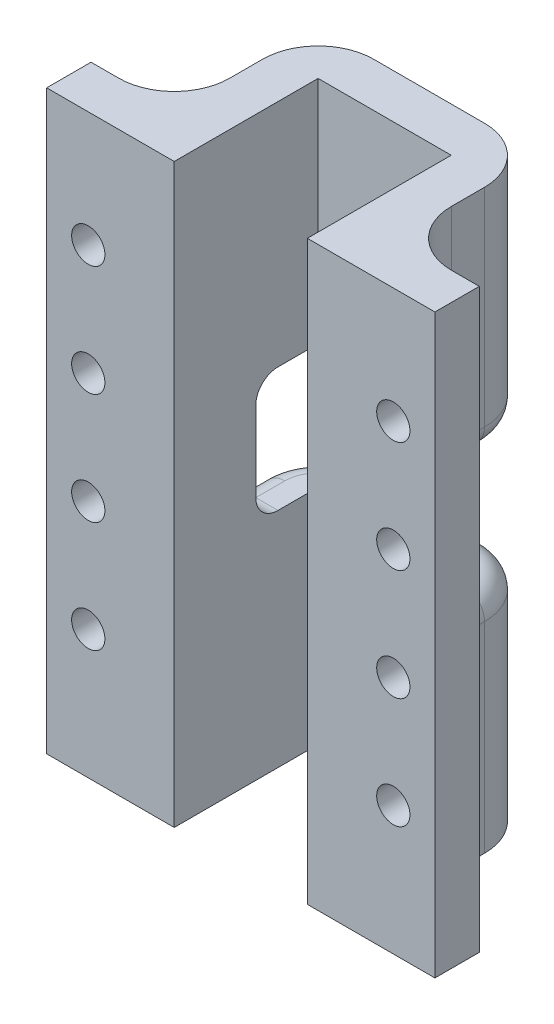
SolidWorks part; units mm, degrees
ref_plane "Спереди" through (0, 0, 0) normal (0, 0, 1) x (1, 0, 0)
ref_plane "Сверху" through (0, 0, 0) normal (0, 1, 0) x (1, 0, 0)
ref_plane "Справа" through (0, 0, 0) normal (1, 0, 0) x (0, 0, -1)
sketch "Эскиз1" plane through (0, 0, 0) normal (0, 1, 0) x (1, 0, 0)
  line L0 (-17.5, -8.4853) -> (-6, -8.4853)
  line L2 (-6, -8.4853) -> (-6, 4.5147)
  line L3 (-6, 4.4853) -> (6, 4.4853)
  line L4 (6, -8.4853) -> (6, 4.4853)
  line L5 (6, -8.4853) -> (17.5, -8.4853)
  line L6 (17.5, -8.4853) -> (17.5, -4.4853)
  line L7 (17.5, -4.4853) -> (10, -4.4853)
  line L8 (10, -4.4853) -> (10, 8.4853)
  line L9 (10, 8.4853) -> (-10, 8.4853)
  line L10 (-10, 8.4853) -> (-10, -4.4853)
  line L11 (-10, -4.4853) -> (-17.5, -4.4853)
  line L12 (-17.5, -4.4853) -> (-17.5, -8.4853)
  dimension "D1" = 11.5
  dimension "D2" = 4
  dimension "D3" = 12.9706
  dimension "D4" = 4
  dimension "D5" = 4
  dimension "D6" = 12.9706
extrude "Бобышка-Вытянуть1" add sketch "Эскиз1" along normal blind 52 contours L11 L12 L0 L2 L3 L4 L5 L6 L7 L8 L9 L10 | L3 L4 L5 L6 L7 L8 L9 L10 L11 L12 L0 L2 region at (-17.111, 0, 6.4853)
fillet "Скругление1" radius 5 4 edges at (-10, 26, -8.4853) (10, 26, -8.4853) (-10, 26, 4.4853) (10, 26, 4.4853)
ref_plane "Плоскость1" through (0, 0, 18.4853) normal (0, 0, 1) x (1, 0, 0)
ref_plane "Плоскость2" through (0, 0, 4.4853) normal (0, 0, -1) x (-1, 0, 0)
sketch "Эскиз2" plane through (0, 0, 4.4853) normal (0, 0, -1) x (-1, 0, 0)
  line L0 (13.75, 52) -> (13.75, 0) construction
  line L10 (-13.75, 52) -> (-13.75, 0) construction
  circle A8 centre (13.75, 41.6) radius 1.5
  circle A9 centre (13.75, 31.6) radius 1.5
  circle A10 centre (13.75, 21.6) radius 1.5
  circle A11 centre (13.75, 11.6) radius 1.5
  circle A12 centre (-13.75, 41.6) radius 1.5
  circle A13 centre (-13.75, 31.6) radius 1.5
  circle A14 centre (-13.75, 21.6) radius 1.5
  circle A15 centre (-13.75, 11.6) radius 1.5
  dimension "D4" = 4
  dimension "D3" = 4
extrude "Вырез-Вытянуть1" cut sketch "Эскиз2" against normal blind 10 and the other way blind 10
sketch "Эскиз3" plane through (0, 0, 4.4853) normal (0, 0, -1) x (-1, 0, 0)
  line L0 (0, 52) -> (0, 0) construction
  line L1 (13.75, 38.4246) -> (16.5, 40.0123)
  line L2 (16.5, 40.0123) -> (16.5, 43.1877)
  line L3 (16.5, 43.1877) -> (13.75, 44.7754)
  line L4 (13.75, 44.7754) -> (11, 43.1877)
  line L5 (11, 43.1877) -> (11, 40.0123)
  line L6 (11, 40.0123) -> (13.75, 38.4246)
  line L7 (-5, 52) -> (5, 52) construction
  line L8 (-11, 40.0123) -> (-13.75, 38.4246)
  line L9 (-11, 43.1877) -> (-11, 40.0123)
  line L10 (-13.75, 44.7754) -> (-11, 43.1877)
  line L11 (-16.5, 43.1877) -> (-13.75, 44.7754)
  line L12 (-16.5, 40.0123) -> (-16.5, 43.1877)
  line L13 (-13.75, 38.4246) -> (-16.5, 40.0123)
  line L14 (13.75, 28.4246) -> (16.5, 30.0123)
  line L15 (16.5, 30.0123) -> (16.5, 33.1877)
  line L16 (16.5, 33.1877) -> (13.75, 34.7754)
  line L17 (13.75, 34.7754) -> (11, 33.1877)
  line L18 (11, 33.1877) -> (11, 30.0123)
  line L19 (11, 30.0123) -> (13.75, 28.4246)
  line L20 (-11, 30.0123) -> (-13.75, 28.4246)
  line L21 (-13.75, 28.4246) -> (-16.5, 30.0123)
  line L22 (-16.5, 30.0123) -> (-16.5, 33.1877)
  line L23 (-16.5, 33.1877) -> (-13.75, 34.7754)
  line L24 (-13.75, 34.7754) -> (-11, 33.1877)
  line L25 (-11, 33.1877) -> (-11, 30.0123)
  line L26 (13.75, 18.4246) -> (16.5, 20.0123)
  line L27 (16.5, 20.0123) -> (16.5, 23.1877)
  line L28 (16.5, 23.1877) -> (13.75, 24.7754)
  line L29 (13.75, 24.7754) -> (11, 23.1877)
  line L30 (11, 23.1877) -> (11, 20.0123)
  line L31 (11, 20.0123) -> (13.75, 18.4246)
  line L32 (-11, 20.0123) -> (-13.75, 18.4246)
  line L33 (-13.75, 18.4246) -> (-16.5, 20.0123)
  line L34 (-16.5, 20.0123) -> (-16.5, 23.1877)
  line L35 (-16.5, 23.1877) -> (-13.75, 24.7754)
  line L36 (-13.75, 24.7754) -> (-11, 23.1877)
  line L37 (-11, 23.1877) -> (-11, 20.0123)
  line L38 (13.75, 8.4246) -> (16.5, 10.0123)
  line L39 (16.5, 10.0123) -> (16.5, 13.1877)
  line L40 (16.5, 13.1877) -> (13.75, 14.7754)
  line L41 (13.75, 14.7754) -> (11, 13.1877)
  line L42 (11, 13.1877) -> (11, 10.0123)
  line L43 (11, 10.0123) -> (13.75, 8.4246)
  line L44 (-11, 10.0123) -> (-13.75, 8.4246)
  line L45 (-13.75, 8.4246) -> (-16.5, 10.0123)
  line L46 (-16.5, 10.0123) -> (-16.5, 13.1877)
  line L47 (-16.5, 13.1877) -> (-13.75, 14.7754)
  line L48 (-13.75, 14.7754) -> (-11, 13.1877)
  line L49 (-11, 13.1877) -> (-11, 10.0123)
  circle A0 centre (13.75, 41.6) radius 2.75 construction
  dimension "D1" = 5.5
extrude "Вырез-Вытянуть2" cut sketch "Эскиз3" against normal blind 1.5 and the other way blind 10
sketch "Эскиз4" plane through (-17.5, 0, 0) normal (-1, 0, 0) x (0, 0, 1)
  line L1 (1.1361, 20.0799) -> (-11.9234, 20.0799)
  line L3 (1.1361, 31.2802) -> (-11.9234, 31.2802)
  line L4 (-11.9234, 20.0799) -> (-11.9234, 31.2802)
  line L5 (1.1361, 20.0799) -> (1.1361, 31.2802)
extrude "Вырез-Вытянуть3" cut sketch "Эскиз4" against normal blind 34
fillet "Скругление2" radius 2 4 edges at (8.1402, 31.2802, 1.1361) (8.1402, 20.0799, 1.1361) (-8.1402, 31.2802, 1.1361) (-8.1402, 20.0799, 1.1361)
fillet "Скругление3" radius 2 20 edges at (-8.5355, 20.0799, -7.0208) (-10, 20.0799, -2.1746) (-10, 20.0876, -0.6886) (-10.1566, 20.8677, 0.7269) (-10.2804, 25.68, 1.1361) (-10.1273, 30.6362, 0.6062) (-10, 31.2725, -0.6886) (-10, 31.2802, -2.1746) (-8.5355, 31.2802, -7.0208) (0, 31.2802, -8.4853) (8.5355, 31.2802, -7.0208) (10, 31.2802, -2.1746) (10, 31.2725, -0.6886) (10.1566, 30.4923, 0.7269) (10.2804, 25.68, 1.1361) (10.1273, 20.7238, 0.6062) (10, 20.0876, -0.6886) (10, 20.0799, -2.1746) (8.5355, 20.0799, -7.0208) (0, 20.0799, -8.4853)
